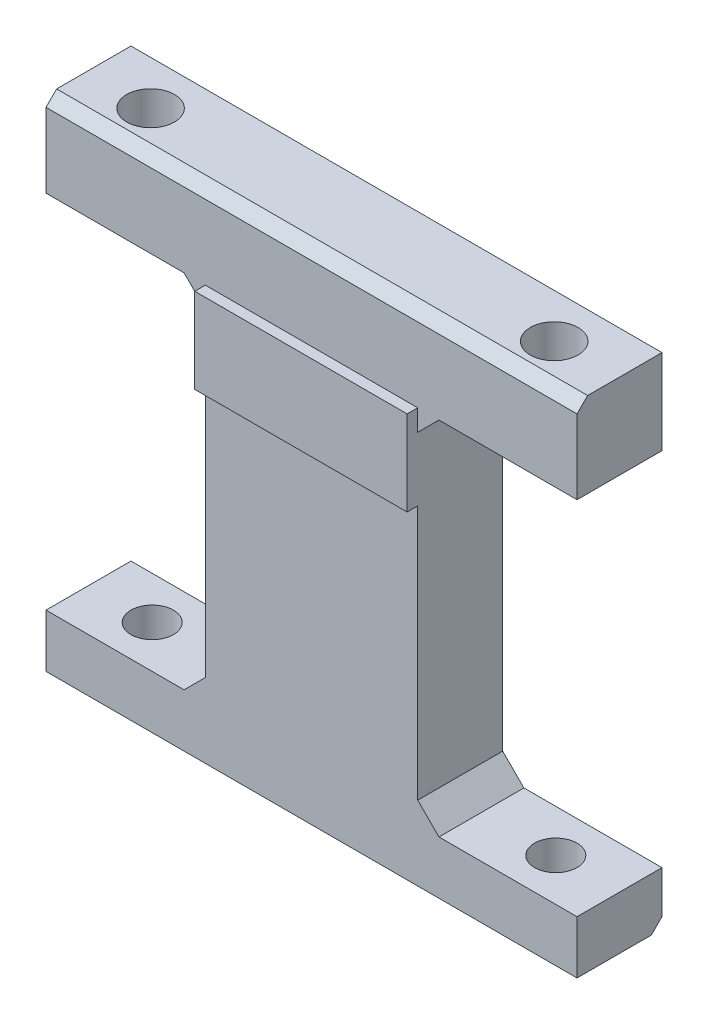
SolidWorks part; units mm, degrees
ref_plane "正面" through (0, 0, 0) normal (0, 0, 1) x (1, 0, 0)
ref_plane "平面" through (0, 0, 0) normal (0, 1, 0) x (1, 0, 0)
ref_plane "右側面" through (0, 0, 0) normal (1, 0, 0) x (0, 0, -1)
sketch "ｽｹｯﾁ1" plane through (0, 0, 0) normal (0, 0, 1) x (1, 0, 0)
  line L0 (0, 0) -> (0, 47) construction
  line L1 (0, 0) -> (25, 0)
  line L2 (25, 0) -> (25, 5)
  line L3 (25, 5) -> (-25, 5)
  line L4 (-25, 5) -> (-25, 0)
  line L5 (-25, 0) -> (0, 0)
  line L6 (0, 5) -> (10, 5)
  line L7 (10, 5) -> (10, 39)
  line L8 (10, 39) -> (-10, 39)
  line L9 (-10, 39) -> (-10, 5)
  line L10 (-10, 5) -> (0, 5)
  line L11 (-25, 39) -> (25, 39)
  line L12 (25, 39) -> (25, 47)
  line L13 (25, 47) -> (-25, 47)
  line L14 (-25, 47) -> (-25, 39)
  line L16 (-10, 39) -> (10, 39)
  line L17 (-10, 39) -> (10, 39)
  line L18 (-10, 39) -> (-10, 33)
  line L19 (-10, 33) -> (10, 33)
  line L20 (10, 39) -> (10, 33)
  dimension "D1" = 25
  dimension "D2" = 25
  dimension "D3" = 5
  dimension "D4" = 10
  dimension "D5" = 10
  dimension "D6" = 25
  dimension "D7" = 25
  dimension "D8" = 39
  dimension "D9" = 8
  dimension "D10" = 6
extrude "ﾎﾞｽ - 押し出し1" add sketch "ｽｹｯﾁ1" against normal blind 8 contours L11 L12 L13 L14 | L10 L6 L7 L8 L9 | L5 L1 L2 L3 L4
sketch "ｽｹｯﾁ2" plane through (0, 5, 0) normal (0, 1, 0) x (1, 0, 0)
  line L0 (0, 0) -> (0, 8) construction
  line L1 (25, 8) -> (-25, 8) construction
  line L2 (0, 4) -> (25, 4) construction
  line L3 (25, 8) -> (25, 0) construction
  line L4 (0, 4) -> (-25, 4) construction
  line L5 (-25, 8) -> (-25, 0) construction
  circle A0 centre (19, 4) radius 2
  circle A1 centre (-19, 4) radius 2
  dimension "D3" = 4
  dimension "D1" = 19
  dimension "D2" = 19
extrude "ｶｯﾄ - 押し出し1" cut sketch "ｽｹｯﾁ2" against normal blind 8
sketch "ｽｹｯﾁ3" plane through (0, 0, 0) normal (0, 0, 1) x (1, 0, 0)
  line L0 (10, 5) -> (10, 39) construction
  line L1 (-10, 39) -> (10, 39)
  line L2 (-10, 39) -> (-10, 31)
  line L3 (-10, 31) -> (10, 31)
  line L4 (10, 39) -> (10, 31)
  dimension "D1" = 8
extrude "ﾎﾞｽ - 押し出し2" add sketch "ｽｹｯﾁ3" along normal blind 1
sketch "ｽｹｯﾁ4" plane through (0, 47, 0) normal (0, 1, 0) x (1, 0, 0)
  circle A0 centre (19, 3.8474) radius 2.25
  circle A1 centre (-19, 3.8474) radius 2.25
  dimension "D3" = 4.5
  dimension "D1" = 19
  dimension "D2" = 19
extrude "ｶｯﾄ - 押し出し2" cut sketch "ｽｹｯﾁ4" against normal blind 10 contours A0
extrude "ｶｯﾄ - 押し出し3" cut sketch "ｽｹｯﾁ4<3>" against normal blind 10
sketch "ｽｹｯﾁ4<3>" plane through (0, 47, 0) normal (0, 1, 0) x (1, 0, 0) same geometry as "ｽｹｯﾁ4"
chamfer "面取り1" distance 2 angle 45 4 edges at (10, 39, -4) (-10, 39, -4) (10, 5, -4) (-10, 5, -4)
chamfer "面取り2" distance 1 angle 45 1 edges at (0, 47, 0)
chamfer "面取り3" distance 1 angle 45 1 edges at (0, 0, -8)
